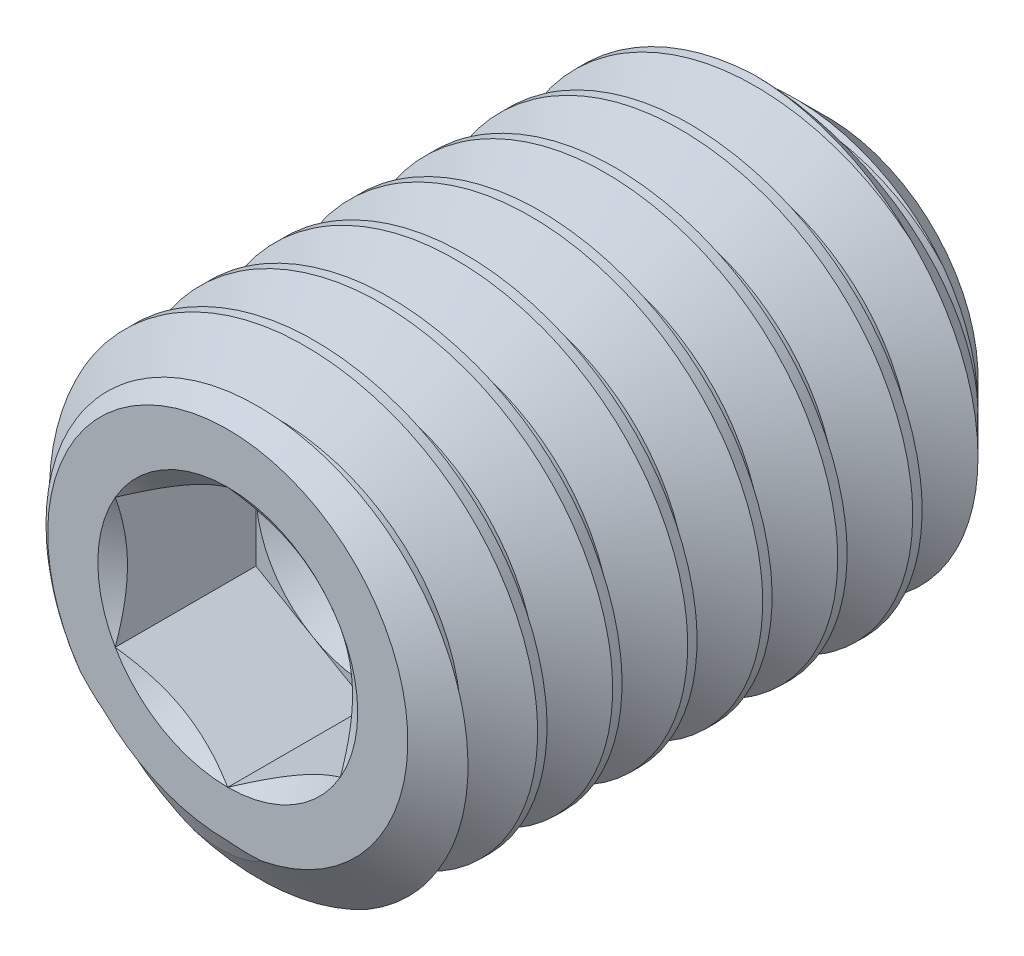
SolidWorks part; units mm, degrees
ref_plane "Front" through (0, 0, 0) normal (0, 0, 1) x (1, 0, 0)
ref_plane "Top" through (0, 0, 0) normal (0, 1, 0) x (1, 0, 0)
ref_plane "Right" through (0, 0, 0) normal (1, 0, 0) x (0, 0, -1)
sketch "Body Sketch" plane through (0, 0, 0) normal (1, 0, 0) x (0, 0, -1)
  line L0 (-2, 0) -> (-2, 1.2)
  line L1 (-2, 1.2) -> (-1.7899, 1.5)
  line L2 (-1.7899, 1.5) -> (1.5, 1.5)
  line L3 (1.5, 1.5) -> (2, 1)
  line L4 (-0.145, 1.5) -> (-0.145, -1.5) construction
  line L5 (2, 0) -> (-2, 0)
  line L6 (-2, 1.2) -> (-2, -1.2) construction
  line L7 (2, 0) -> (2, 1)
  point P11 (-0.145, 0)
  dimension "Length" = 4
  dimension "D3" = 35
  dimension "D6" = 45
  dimension "Diameter" = 3
  dimension "D1" = 2.4
  dimension "D2" = 0.5
revolve "Body Revolve" add sketch "Body Sketch" angle 360 about L5
ref_plane "Plane1" through (0, 0, -2) normal (0, 0, 1) x (1, 0, 0)
sketch "Sketch27" plane through (0, 0, -2) normal (0, 0, 1) x (1, 0, 0)
  circle A0 centre (0, 0) radius 1.5 construction
  circle A1 centre (0, 0) radius 1.5
curve "Helix/Spiral" pitch 0.5 height 4.5 radius 1.5 centre (0, 0, -2) axis (0, 0, 1) start towards (0, 1, 0) parameters "Thread Pitch"=0.5
sketch "Sketch28" plane through (0, 0, 0) normal (1, 0, 0) x (0, 0, -1)
  line L0 (2, 1.5) -> (2.4375, 1.5)
  line L1 (2.4375, 1.5) -> (2.25, 1.1752)
  line L2 (2.25, 1.1752) -> (2.1875, 1.1752)
  line L3 (2.1875, 1.1752) -> (2, 1.5)
  line L4 (2.0937, 1.3376) -> (2.3437, 1.3376) construction
  line L6 (-1.7899, 1.5) -> (1.5, 1.5) construction
  dimension "D1" = 0.0625
  dimension "D3" = 60
  dimension "D2" = 0.25
sweep "Cut Sweep" cut profiles "Sketch28" path "Helix/Spiral" align with end faces yes
sketch "Hex Sketch" plane through (0, 0, 2) normal (0, 0, 1) x (1, 0, 0)
  line L1 (0, 0.866) -> (-0.75, 0.433)
  line L2 (-0.75, 0.433) -> (-0.75, -0.433)
  line L3 (-0.75, -0.433) -> (0, -0.866)
  line L4 (0, -0.866) -> (0.75, -0.433)
  line L5 (0.75, -0.433) -> (0.75, 0.433)
  line L6 (0.75, 0.433) -> (0, 0.866)
  circle A0 centre (0, 0) radius 0.75 construction
  dimension "Hex" = 1.5
extrude "Hex Extrude" cut sketch "Hex Sketch" against normal blind 0.9375
sketch "Hex Entry Sketch" plane through (0, 0, 2) normal (0, 0, 1) x (1, 0, 0)
  circle A0 centre (0, 0) radius 0.866
extrude "Hex Entry Extrude" cut sketch "Hex Entry Sketch" against normal through all draft 55
sketch "Hex Bottom Sketch" plane through (0, 0, 1.0625) normal (0, 0, 1) x (1, 0, 0)
  circle A0 centre (0, 0) radius 0.75 construction
  circle A1 centre (0, 0) radius 0.75
extrude "Hex Bottom Extrude" cut sketch "Hex Bottom Sketch" against normal through all draft 60
equation "\"D1@Sketch28\" = \"Thread Pitch@Helix/Spiral\" * .125"
equation "\"D2@Sketch28\" = \"Thread Pitch@Helix/Spiral\" * .5"
equation "\"D3@Helix/Spiral\" = \"Length@Body Sketch\" + \"Thread Pitch@Helix/Spiral\""
equation "\"hex Depth@Hex Extrude\" = \"Hex@Hex Sketch\" * .625"
equation "\"D1@Body Sketch\" = \"Diameter@Body Sketch\" * .8"
equation "\"D2@Body Sketch\" = \"Thread Pitch@Helix/Spiral\""
equation "\"Diameter\"= 3mm"
equation "\"Thread Pitch\"= 0.5mm"
equation "\"Hex Size\"= 1.5mm"
equation "\"Diameter@Body Sketch\"=\"Diameter\""
equation "\"Chamfer Size\"= 0.5mm"
equation "\"Thread Pitch@Helix/Spiral\" = \"Thread Pitch\""
equation "\"Hex@Hex Sketch\" = \"Hex Size\""
